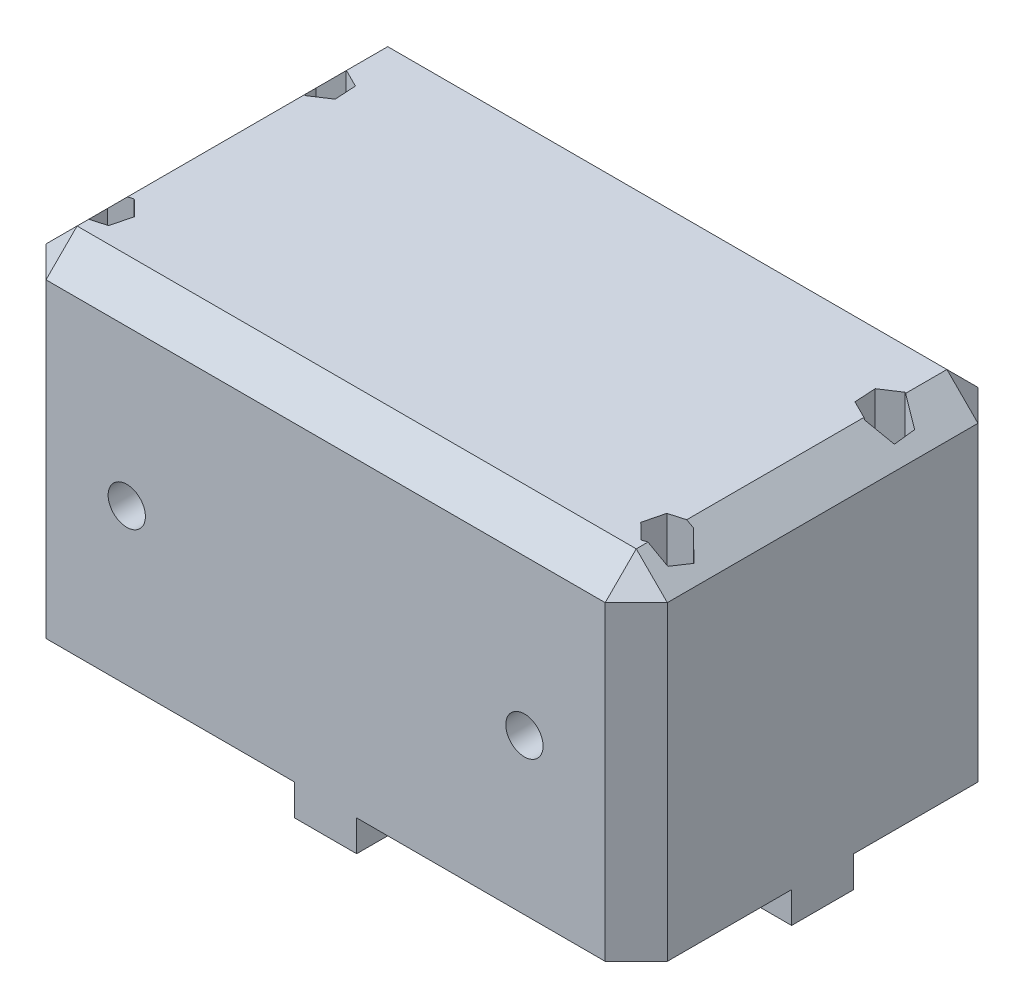
SolidWorks part; units mm, degrees
ref_plane "Płaszczyzna przednia" through (0, 0, 0) normal (0, 0, 1) x (1, 0, 0)
ref_plane "Płaszczyzna górna" through (0, 0, 0) normal (0, 1, 0) x (1, 0, 0)
ref_plane "Płaszczyzna prawa" through (0, 0, 0) normal (1, 0, 0) x (0, 0, -1)
sketch "Sketch1" plane through (0, 0, 0) normal (0, 1, 0) x (1, 0, 0)
  line L1 (-50, -30) -> (50, -30)
  line L2 (-50, -30) -> (-50, 30)
  line L3 (-50, 30) -> (50, 30)
  line L4 (50, -30) -> (50, 30)
  line L5 (-50, -30) -> (50, 30) construction
  line L6 (-50, 30) -> (50, -30) construction
  point P0 (0, 0)
  dimension "D1" = 100
  dimension "D2" = 60
extrude "Boss-Extrude1" add sketch "Sketch1" along normal blind 55
sketch "Sketch2" plane through (0, 0, 0) normal (0, 0, 1) x (1, 0, 0)
  line L0 (-50, 55) -> (-50, 0) construction
  line L1 (-40, -50) -> (40, -50)
  line L2 (-40, -50) -> (-40, 50)
  line L3 (-40, 50) -> (40, 50)
  line L4 (40, -50) -> (40, 50)
  line L5 (-40, -50) -> (40, 50) construction
  line L6 (-40, 50) -> (40, -50) construction
  line L7 (50, 55) -> (50, 0) construction
  line L8 (-50, 55) -> (50, 55) construction
  point P0 (0, 0)
  dimension "D1" = 10
  dimension "D2" = 10
  dimension "D3" = 5
extrude "Cut-Extrude1" cut sketch "Sketch2" along normal blind 45 from surface starting at face at (0, 27.5, -30)
sketch "Sketch3" plane through (0, 0, 0) normal (0, 1, 0) x (1, 0, 0)
  line L0 (-50, 30) -> (-50, -30) construction
  line L1 (-45, -20) -> (45, -20) construction
  line L2 (-45, -20) -> (-45, 15) construction
  line L3 (-45, 15) -> (45, 15) construction
  line L4 (45, -20) -> (45, 15) construction
  line L5 (-45, -20) -> (45, 15) construction
  line L6 (-45, 15) -> (45, -20) construction
  line L8 (50, 30) -> (-50, 30) construction
  line L9 (-50, -30) -> (50, -30) construction
  line L10 (50, -30) -> (50, 30) construction
  circle A0 centre (-45, 15) radius 1.75
  circle A1 centre (45, 15) radius 1.75
  circle A2 centre (45, -20) radius 1.75
  circle A3 centre (-45, -20) radius 1.75
  point P0 (0, 0)
  dimension "D4" = 3.5
  dimension "D1" = 5
  dimension "D2" = 5
  dimension "D3" = 15
  dimension "D5" = 10
extrude "Cut-Extrude2" cut sketch "Sketch3" along normal through all both and the other way through all
sketch "Sketch4" plane through (0, 0, 0) normal (0, 1, 0) x (1, 0, 0)
  line L1 (44.1597, -23.3606) -> (47.4902, -22.4081)
  line L2 (47.4902, -22.4081) -> (48.3306, -19.0474)
  line L3 (48.3306, -19.0474) -> (45.8403, -16.6394)
  line L4 (45.8403, -16.6394) -> (42.5098, -17.5919)
  line L5 (42.5098, -17.5919) -> (41.6694, -20.9526)
  line L6 (41.6694, -20.9526) -> (44.1597, -23.3606)
  line L7 (44.7946, 18.458) -> (41.9026, 16.5511)
  line L8 (41.9026, 16.5511) -> (42.108, 13.0931)
  line L9 (42.108, 13.0931) -> (45.2054, 11.542)
  line L10 (45.2054, 11.542) -> (48.0974, 13.4489)
  line L11 (48.0974, 13.4489) -> (47.892, 16.9069)
  line L12 (47.892, 16.9069) -> (44.7946, 18.458)
  line L13 (-45.8403, -23.3606) -> (-42.5098, -22.4081)
  line L14 (-42.5098, -22.4081) -> (-41.6694, -19.0474)
  line L15 (-41.6694, -19.0474) -> (-44.1597, -16.6394)
  line L16 (-44.1597, -16.6394) -> (-47.4902, -17.5919)
  line L17 (-47.4902, -17.5919) -> (-48.3306, -20.9526)
  line L18 (-48.3306, -20.9526) -> (-45.8403, -23.3606)
  line L19 (-45.2054, 18.458) -> (-48.0974, 16.5511)
  line L20 (-48.0974, 16.5511) -> (-47.892, 13.0931)
  line L21 (-47.892, 13.0931) -> (-44.7946, 11.542)
  line L22 (-44.7946, 11.542) -> (-41.9026, 13.4489)
  line L23 (-41.9026, 13.4489) -> (-42.108, 16.9069)
  line L24 (-42.108, 16.9069) -> (-45.2054, 18.458)
  circle A0 centre (45, -20) radius 3 construction
  circle A1 centre (45, 15) radius 3 construction
  circle A2 centre (-45, -20) radius 3 construction
  circle A3 centre (-45, 15) radius 3 construction
  dimension "D1" = 6
  dimension "D2" = 6
  dimension "D3" = 6
  dimension "D4" = 6
extrude "Cut-Extrude3" cut sketch "Sketch4" against normal blind 52 from surface starting at face at (-45, 55, 21.75)
sketch "Sketch5" plane through (0, 0, 0) normal (0, 0, 1) x (1, 0, 0)
  line L0 (38.5, 25) -> (-40, 25) construction
  line L2 (-40, 50) -> (-40, 0) construction
  line L9 (-40, 15) -> (-37, 15)
  line L11 (40, 15) -> (37, 15)
  line L12 (40, 15) -> (40, 35)
  line L13 (40, 35) -> (37, 35)
  line L14 (37, 15) -> (37, 35)
  line L15 (40, 15) -> (37, 35) construction
  line L16 (40, 35) -> (37, 15) construction
  line L18 (40, 0) -> (40, 50) construction
  line L19 (-40, 15) -> (-40, 35)
  line L20 (-40, 35) -> (-37, 35)
  line L21 (-37, 15) -> (-37, 35)
  line L22 (-40, 15) -> (-37, 35) construction
  line L23 (-40, 35) -> (-37, 15) construction
  point P6 (-38.5, 25)
  dimension "D1" = 3
  dimension "D2" = 20
  dimension "D3" = 20
  dimension "D4" = 3
extrude "Boss-Extrude2" add sketch "Sketch5" against normal up to surface (30 mm away) from surface up to face at (0, 26.25, -30) starting at face at (0, 25, 15)
chamfer "Chamfer1" distance 3 angle 45 4 edges at (37, 15, -7.5) (37, 35, -7.5) (-37, 15, -7.5) (-37, 35, -7.5)
sketch "Sketch6" plane through (0, 0, 0) normal (0, 0, 1) x (1, 0, 0)
  line L0 (37, 25) -> (-37, 25) construction
  line L1 (37, 18) -> (37, 32) construction
  line L3 (32, 50) -> (32, 0) construction
  line L9 (-37, 18) -> (-37, 32) construction
  line L10 (37, 32) -> (37, 18) construction
  line L11 (-37, 32) -> (-37, 18) construction
  circle A0 centre (32, 25) radius 1.75
  circle A1 centre (-32, 25) radius 1.75
  dimension "D1" = 3.5
  dimension "D2" = 5
  dimension "D3" = 5
extrude "Cut-Extrude4" cut sketch "Sketch6" against normal through all both and the other way through all
sketch "Sketch7" plane through (0, 0, 0) normal (0, 0, 1) x (1, 0, 0)
  circle A0 centre (-32, 25) radius 3
  circle A1 centre (32, 25) radius 3
  dimension "D1" = 6
extrude "Cut-Extrude5" cut sketch "Sketch7" against normal blind 5 from surface starting at face at (33.75, 25, 30)
sketch "Sketch8" plane through (0, 0, 0) normal (1, 0, 0) x (0, 0, -1)
  line L0 (-5, 0) -> (5, 0)
  line L1 (-5, 0) -> (-5, -5)
  line L2 (5, 0) -> (5, -5)
  line L3 (-5, -5) -> (5, -5)
  line L4 (-30, 0) -> (30, 0) construction
  dimension "D1" = 10
  dimension "D2" = 5
  dimension "D3" = 25
extrude "Boss-Extrude3" add sketch "Sketch8" against normal blind 5 from surface starting at face at (50, 27.5, 0)
extrude "Boss-Extrude4" add sketch "Sketch8<2>" along normal blind 5 from surface starting at face at (-50, 27.5, 0)
sketch "Sketch8<2>" plane through (0, 0, 0) normal (1, 0, 0) x (0, 0, -1) same geometry as "Sketch8"
sketch "Sketch9" plane through (0, 0, 0) normal (0, 0, 1) x (1, 0, 0)
  line L0 (-5, 0) -> (5, 0)
  line L1 (-5, 0) -> (-5, -5)
  line L2 (5, 0) -> (5, -5)
  line L3 (-5, -5) -> (5, -5)
  line L4 (-50, 0) -> (50, 0) construction
  line L5 (-50, 55) -> (-50, 0) construction
  dimension "D1" = 45
  dimension "D2" = 5
  dimension "D3" = 10
extrude "Boss-Extrude5" add sketch "Sketch9" against normal blind 5 from surface starting at face at (-35, 25, 30)
chamfer "Chamfer2" distance 5 angle 45 8 edges at (-50, 27.5, -30) (50, 27.5, -30) (50, 27.5, 30) (50, 55, 0) (-50, 55, 0) (0, 55, 30) (-50, 27.5, 30) (0, 55, -30)
